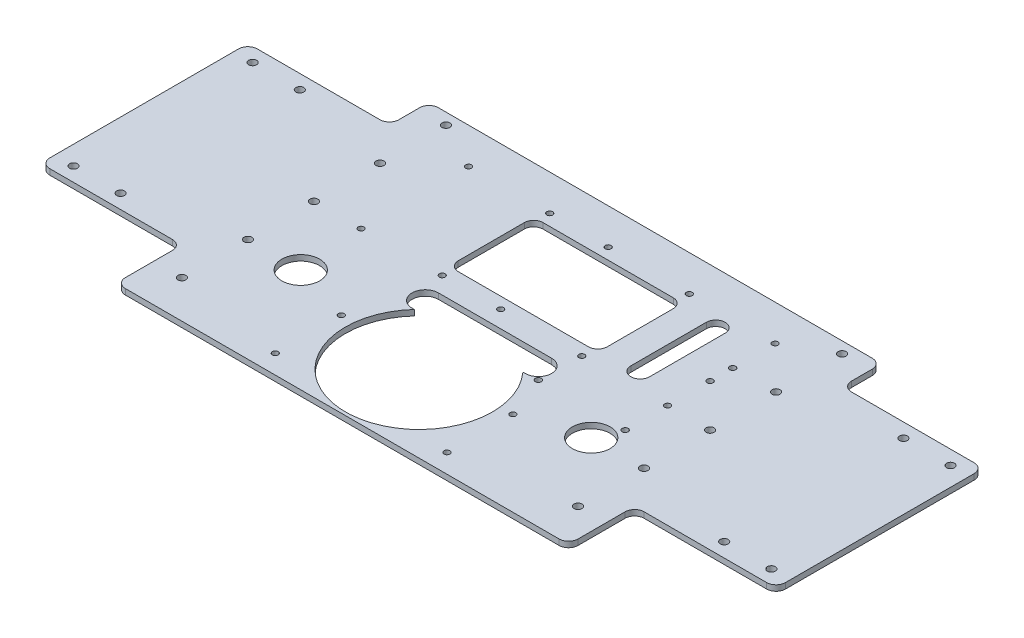
SolidWorks part; units mm, degrees
material "Thornel Mat VMA"
ref_plane "前视基准面" through (0, 0, 0) normal (0, 0, 1) x (1, 0, 0)
ref_plane "上视基准面" through (0, 0, 0) normal (0, 1, 0) x (1, 0, 0)
ref_plane "右视基准面" through (0, 0, 0) normal (1, 0, 0) x (0, 0, -1)
sketch "草图1" plane through (0, 0, 0) normal (0, 1, 0) x (1, 0, 0)
  line L0 (31.5759, -198.8718) -> (31.5759, 46.1282) construction
  line L1 (151.5759, -32.8718) -> (-88.4241, -32.8718)
  line L7 (-88.4241, -198.8718) -> (151.5759, -198.8718)
  line L8 (-88.4241, -198.8718) -> (-88.4241, -32.8718)
  line L10 (151.5759, -198.8718) -> (151.5759, -32.8718)
  line L16 (6.5759, -59.8718) -> (56.5759, -59.8718) construction
  line L18 (6.5759, -34.8718) -> (6.5759, -84.8718) construction
  line L19 (6.5759, -84.8718) -> (56.5759, -84.8718) construction
  line L20 (56.5759, -34.8718) -> (56.5759, -84.8718) construction
  line L21 (151.5759, -94.8718) -> (-88.4241, -94.8718) construction
  line L22 (-88.4241, -49.8718) -> (151.5759, -49.8718) construction
  circle A5 centre (6.5759, -84.8718) radius 1.6 construction
  circle A6 centre (56.5759, -84.8718) radius 1.6 construction
  point P6 (0, -121.2547)
  dimension "D2" = 166
  dimension "D4" = 240
  dimension "D9" = 10
  dimension "D12" = 50
  dimension "D15" = 45
extrude "构型与裁判孔" add sketch "草图1" along normal blind 3 contours L10 L21 L8 L7 region at (31.5759, 0, 115.8718)
sketch "草图4" plane through (0, 3, 0) normal (0, 1, 0) x (1, 0, 0)
  line L0 (-73.4241, -108.8718) -> (-73.4241, -198.8718) construction
  line L1 (77.0759, -32.8718) -> (77.0759, -198.8718) construction
  line L2 (151.5759, -32.8718) -> (-88.4241, -32.8718) construction
  line L3 (-88.4241, -198.8718) -> (-88.4241, -32.8718) construction
  line L4 (31.5759, -32.8718) -> (31.5759, -198.8718) construction
  line L5 (-88.4241, -198.8718) -> (151.5759, -198.8718) construction
  line L6 (-13.9241, -32.8718) -> (-13.9241, -198.8718) construction
  line L7 (-88.4241, -198.8718) -> (151.5759, -198.8718) construction
  line L8 (-88.4241, -198.8718) -> (151.5759, -198.8718) construction
  circle A0 centre (-73.4241, -73.8718) radius 2.1
  circle A1 centre (136.5759, -178.8718) radius 2.1
  circle A2 centre (-73.4241, -108.8718) radius 2.1
  circle A3 centre (-73.4241, -143.8718) radius 2.1
  circle A4 centre (-73.4241, -178.8718) radius 2.1
  circle A5 centre (136.5759, -143.8718) radius 2.1
  circle A6 centre (136.5759, -108.8718) radius 2.1
  circle A7 centre (136.5759, -73.8718) radius 2.1
  circle A8 centre (-73.4241, -38.8718) radius 2.1
  circle A9 centre (136.5759, -38.8718) radius 2.1
  circle A10 centre (77.0759, -188.8718) radius 1.55
  circle A11 centre (-13.9241, -188.8718) radius 1.55
  circle A12 centre (77.0759, -153.8718) radius 1.55
  circle A13 centre (-13.9241, -153.8718) radius 1.55
  dimension "D2" = 20
  dimension "D5" = 35
  dimension "D6" = 35
  dimension "D7" = 35
  dimension "D3" = 4.2
  dimension "D4" = 35
  dimension "D8" = 3.1
  dimension "D9" = 10
  dimension "D10" = 35
  dimension "D1" = 15
  dimension "D11" = 91
extrude "切除-拉伸3" cut sketch "草图4" against normal through all
sketch "草图5" plane through (0, 3, 0) normal (0, 1, 0) x (1, 0, 0)
  line L0 (71.0759, -57.8718) -> (-7.9241, -57.8718)
  line L1 (71.0759, -57.8718) -> (71.0759, -102.8718)
  line L2 (71.0759, -102.8718) -> (-7.9241, -102.8718)
  line L3 (-7.9241, -57.8718) -> (-7.9241, -102.8718)
  line L4 (71.0759, -57.8718) -> (-7.9241, -102.8718) construction
  line L5 (71.0759, -102.8718) -> (-7.9241, -57.8718) construction
  line L6 (31.5759, -32.8718) -> (31.5759, -104.1535) construction
  line L7 (71.0759, -80.3718) -> (-7.9241, -80.3718) construction
  line L8 (31.5759, -57.8718) -> (31.5759, -102.8718) construction
  line L9 (151.5759, -32.8718) -> (-88.4241, -32.8718) construction
  line L10 (91.0759, -100.3718) -> (91.0759, -60.3718) construction
  line L11 (86.0759, -100.3718) -> (86.0759, -60.3718)
  line L12 (96.0759, -100.3718) -> (96.0759, -60.3718)
  line L13 (31.5759, -102.8718) -> (31.5759, -198.8718) construction
  line L16 (-88.4241, -198.8718) -> (151.5759, -198.8718) construction
  line L17 (1.5759, -124.8718) -> (61.5759, -124.8718) construction
  line L18 (1.5759, -117.8718) -> (61.5759, -117.8718)
  line L19 (1.5759, -131.8718) -> (21.5759, -131.8718)
  line L20 (41.5759, -131.8718) -> (61.5759, -131.8718)
  line L21 (-73.4241, -143.8718) -> (136.5759, -143.8718) construction
  circle A0 centre (-5.4241, -51.8718) radius 1.55
  circle A1 centre (68.5759, -51.8718) radius 1.55
  circle A2 centre (68.5759, -108.8718) radius 1.55
  circle A3 centre (-5.4241, -108.8718) radius 1.55
  arc A4 (86.0759, -100.3718) -> (96.0759, -100.3718) centre (91.0759, -100.3718) ccw
  arc A5 (96.0759, -60.3718) -> (86.0759, -60.3718) centre (91.0759, -60.3718) ccw
  arc A8 (1.5759, -117.8718) -> (1.5759, -131.8718) centre (1.5759, -124.8718) ccw
  arc A9 (61.5759, -131.8718) -> (61.5759, -117.8718) centre (61.5759, -124.8718) ccw
  arc A10 (21.5759, -131.8718) -> (41.5759, -131.8718) centre (31.5759, -131.8718) ccw
  circle A11 centre (-45.4241, -143.8718) radius 10
  circle A12 centre (-73.4241, -143.8718) radius 2.1 construction
  circle A13 centre (108.5759, -143.8718) radius 10
  point P1 (110.5236, -62.9669)
  point P23 (91.0759, -80.3718)
  point P33 (31.5759, -124.8718)
  dimension "D3" = 3.1
  dimension "D7" = 5
  dimension "D10" = 7
  dimension "D13" = 20
  dimension "D14" = 28
  dimension "D1" = 79
  dimension "D2" = 45
  dimension "D4" = 37
  dimension "D5" = 28.5
  dimension "D6" = 25
  dimension "D8" = 40
  dimension "D9" = 15
  dimension "D11" = 60
  dimension "D12" = 15
extrude "切除-拉伸4" cut sketch "草图5" against normal through all
sketch "草图9" plane through (0, 0, 0) normal (0, -1, 0) x (1, 0, 0)
  line L0 (-1005.4241, 108.8718) -> (48994.5759, 108.8718) construction
  line L1 (-88.4241, 198.8718) -> (-88.4241, 32.8718) construction
  line L2 (-7.9241, 57.8718) -> (-7.9241, 102.8718) construction
  line L3 (-7.9241, 57.8718) -> (-7.9241, 102.8718) construction
  line L4 (-7.9241, 80.3718) -> (10.0801, 80.3718) construction
  line L5 (-1005.4241, 51.8718) -> (48994.5759, 51.8718) construction
  line L8 (91.0759, 105.3718) -> (91.0759, 78.9227) construction
  circle A0 centre (-5.4241, 108.8718) radius 1.55 construction
  circle A1 centre (-5.4241, 108.8718) radius 1.55 construction
  circle A2 centre (-73.4241, 108.8718) radius 2.1 construction
  circle A3 centre (-73.4241, 108.8718) radius 2.1 construction
  circle A4 centre (68.5759, 108.8718) radius 1.55 construction
  circle A5 centre (68.5759, 108.8718) radius 1.55
  circle A6 centre (-48.4241, 108.8718) radius 1.55
  circle A7 centre (25.5759, 108.8718) radius 1.55
  circle A8 centre (-5.4241, 51.8718) radius 1.55 construction
  circle A9 centre (25.5759, 51.8718) radius 1.55
  circle A10 centre (-48.4241, 51.8718) radius 1.55
  circle A12 centre (114.0759, 51.8718) radius 1.55
  circle A15 centre (68.5759, 51.8718) radius 1.55 construction
  circle A16 centre (114.0759, 74.3718) radius 1.6
  circle A17 centre (136.5759, 38.8718) radius 2.1 construction
  circle A18 centre (114.0759, 86.3718) radius 1.6
  circle A19 centre (114.0759, 108.8718) radius 1.55
  circle A20 centre (114.0759, 131.3718) radius 1.6
  arc A21 (96.0759, 100.3718) -> (86.0759, 100.3718) centre (91.0759, 100.3718) ccw construction
  circle A22 centre (68.0759, 131.3718) radius 1.6
  dimension "D3" = 3.1
  dimension "D5" = 3.1
  dimension "D7" = 3.2
  dimension "D8" = 3.1
  dimension "D9" = 45.5
  dimension "D10" = 22.5
  dimension "D1" = 15
  dimension "D2" = 74
  dimension "D4" = 25
  dimension "D6" = 74
  dimension "D11" = 22.5
sketch "草图6" plane through (0, 0, 0) normal (0, 1, 0) x (1, 0, 0)
  line L0 (-63.0381, -108.8718) -> (146.9619, -108.8718) construction
  line L1 (-88.4241, -53.8718) -> (-163.4241, -53.8718)
  line L2 (-88.4241, -198.8718) -> (-88.4241, -32.8718) construction
  line L3 (-163.4241, -53.8718) -> (-163.4241, -163.8718)
  line L4 (-73.4241, -108.8718) -> (136.5759, -108.8718) construction
  line L5 (-88.4241, -53.8718) -> (-88.4241, -163.8718)
  line L6 (-88.4241, -163.8718) -> (-163.4241, -163.8718)
  line L7 (31.5759, -32.8718) -> (31.5759, -198.8718) construction
  line L8 (151.5759, -32.8718) -> (-88.4241, -32.8718) construction
  line L9 (-88.4241, -198.8718) -> (151.5759, -198.8718) construction
  line L10 (151.5759, -53.8718) -> (151.5759, -163.8718)
  line L11 (151.5759, -163.8718) -> (226.5759, -163.8718)
  line L12 (226.5759, -53.8718) -> (226.5759, -163.8718)
  line L13 (151.5759, -53.8718) -> (226.5759, -53.8718)
  line L14 (-153.4241, -53.8718) -> (-153.4241, -163.8718) construction
  line L15 (-128.4241, -53.8718) -> (-128.4241, -163.8718) construction
  line L16 (-153.4241, -61.3718) -> (-128.4241, -61.3718) construction
  circle A0 centre (-153.4241, -61.3718) radius 2.1
  circle A1 centre (-153.4241, -156.3718) radius 2.1
  circle A2 centre (216.5759, -156.3718) radius 2.1
  circle A3 centre (216.5759, -61.3718) radius 2.1
  circle A4 centre (-128.4241, -61.3718) radius 2.1
  circle A5 centre (-128.4241, -156.3718) radius 2.1
  circle A6 centre (191.5759, -156.3718) radius 2.1
  circle A7 centre (191.5759, -61.3718) radius 2.1
  point P15 (-88.4241, -108.8718)
  point P16 (-163.4241, -108.8718)
  dimension "D4" = 95
  dimension "D6" = 4.2
  dimension "D7" = 4.2
  dimension "D1" = 75
  dimension "D2" = 55
  dimension "D3" = 10
  dimension "D5" = 25
extrude "凸台-拉伸1" add sketch "草图6" along normal blind 3
fillet "圆角1" radius 5 18 edges at (71.0759, 1.5, 102.8718) (-7.9241, 1.5, 102.8718) (-7.9241, 1.5, 57.8718) (71.0759, 1.5, 57.8718) (151.5759, 1.5, 32.8718) (-88.4241, 1.5, 32.8718) (151.5759, 1.5, 53.8718) (151.5759, 1.5, 163.8718) (-88.4241, 1.5, 163.8718) (-88.4241, 1.5, 53.8718) (226.5759, 1.5, 53.8718) (226.5759, 1.5, 163.8718) (151.5759, 1.5, 198.8718) (-88.4241, 1.5, 198.8718) (-163.4241, 1.5, 53.8718) (-163.4241, 1.5, 163.8718) (41.5759, 1.5, 131.8718) (21.5759, 1.5, 131.8718)
sketch "草图7" plane through (0, 3, 0) normal (0, 1, 0) x (1, 0, 0)
  line L0 (146.5759, -32.8718) -> (-83.4241, -32.8718) construction
  line L1 (-48.4241, -32.8718) -> (-48.4241, -82.8718)
  line L2 (-88.4241, -48.8718) -> (-88.4241, -37.8718) construction
  line L3 (-93.4241, -82.8718) -> (-48.4241, -82.8718)
  line L4 (-83.4241, -198.8718) -> (146.5759, -198.8718) construction
  line L5 (31.5759, -198.8718) -> (31.5759, 61.0332) construction
  line L6 (156.5759, -82.8718) -> (111.5759, -82.8718)
  line L7 (151.7733, -149.2908) -> (156.5759, -82.8718)
  line L8 (111.5759, -32.8718) -> (111.5759, -82.8718)
  line L10 (-48.4241, -32.8718) -> (111.5759, -32.8718)
  line L11 (-93.4241, -82.8718) -> (156.5759, -82.8718)
  line L12 (-93.4241, -82.8718) -> (-93.4241, -208.1915)
  line L13 (-93.4241, -208.1915) -> (156.5759, -208.1915)
  line L14 (156.5759, -82.8718) -> (156.5759, -208.1915)
  line L19 (-48.4241, -32.8718) -> (-48.4241, -82.8718)
  line L20 (-48.4241, -82.8718) -> (111.5759, -82.8718)
  line L21 (111.5759, -32.8718) -> (111.5759, -82.8718)
  dimension "D1" = 50
  dimension "D2" = 40
  dimension "D3" = 0
extrude "切除-拉伸5" [suppressed] cut sketch "草图7" against normal blind 10
fillet "圆角2" [suppressed] radius 10
fillet "圆角3" [suppressed] radius 10
sketch "草图8" plane through (0, 3, 0) normal (0, 1, 0) x (1, 0, 0)
  circle A0 centre (31.5759, -158.2052) radius 35.8 construction
  circle A1 centre (31.5759, -158.2052) radius 35.8 construction
  circle A2 centre (31.5759, -158.2052) radius 39
  dimension "D1" = 78
extrude "切除-拉伸6" cut sketch "草图8" against normal blind 10
extrude "切除-拉伸7" cut sketch "草图9" against normal blind 10
